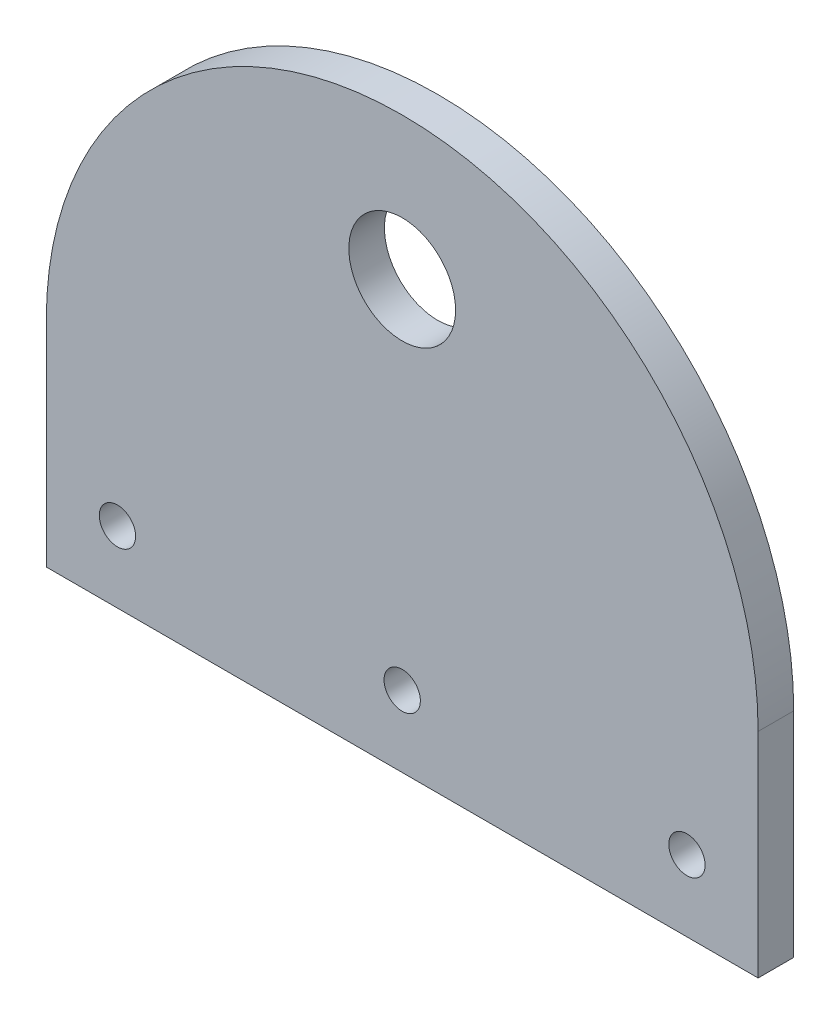
SolidWorks part; units mm, degrees
ref_plane "正面" through (0, 0, 0) normal (0, 0, 1) x (1, 0, 0)
ref_plane "平面" through (0, 0, 0) normal (0, 1, 0) x (1, 0, 0)
ref_plane "右側面" through (0, 0, 0) normal (1, 0, 0) x (0, 0, -1)
sketch "ｽｹｯﾁ1" plane through (0, 0, 0) normal (0, 0, 1) x (1, 0, 0)
  line L0 (-50, -60) -> (50, -60)
  line L1 (-50, -30) -> (-50, -60)
  line L2 (50, -30) -> (50, -60)
  line L3 (0, 0) -> (0, -30) construction
  line L4 (-40, -30) -> (-40, -50) construction
  line L5 (-40, -50) -> (40, -50) construction
  line L6 (40, -50) -> (40, -30) construction
  line L7 (-50, -30) -> (50, -30) construction
  circle A0 centre (0, 0) radius 7.5
  arc A2 (-50, -30) -> (50, -30) centre (0, -30) cw
  circle A3 centre (-40, -50) radius 2.55
  circle A4 centre (0, -50) radius 2.55
  circle A5 centre (40, -50) radius 2.55
  point P15 (40, -48.9562)
  point P18 (-40, -40)
  point P19 (-40, -40)
  point P20 (-40, -46.4565)
  point P22 (0, 0)
  point P23 (0, 0)
  point P24 (-40, -50.4642)
  dimension "D1" = 100
  dimension "D2" = 15
  dimension "D3" = 30
  dimension "D4" = 30
  dimension "D8" = 5.1
  dimension "D5" = 10
  dimension "D6" = 10
  dimension "D7" = 10
extrude "ﾎﾞｽ - 押し出し1" add sketch "ｽｹｯﾁ1" along normal blind 5
